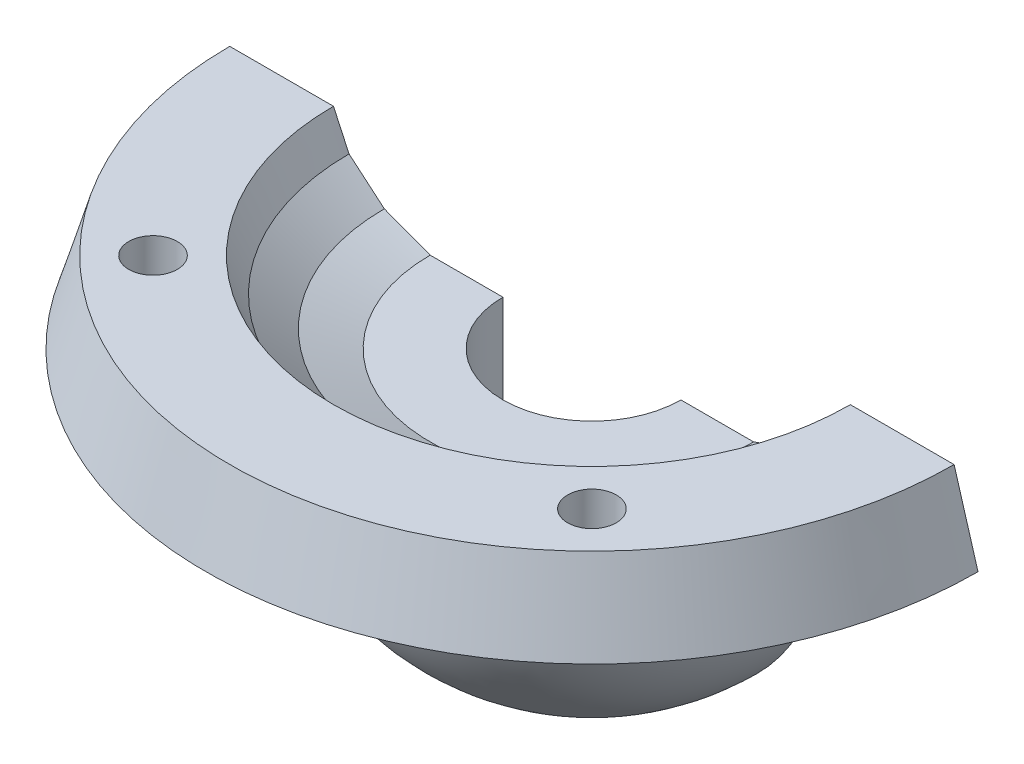
SolidWorks part; units mm, degrees
ref_plane "Front Plane" through (0, 0, 0) normal (0, 0, 1) x (1, 0, 0)
ref_plane "Top Plane" through (0, 0, 0) normal (0, 1, 0) x (1, 0, 0)
ref_plane "Right Plane" through (0, 0, 0) normal (1, 0, 0) x (0, 0, -1)
sketch "Sketch1" plane through (0, 0, 0) normal (0, 0, 1) x (1, 0, 0)
  line L0 (0, -14.5) -> (0, 2) construction
  line L1 (0, -55) -> (0, 55) construction
  line L2 (0, 2) -> (-14.3614, 2)
  line L3 (-5.5, 2) -> (-5.5, -3.5)
  line L4 (-5.5, -3.5) -> (-10, -3.5)
  line L5 (-10, -9.5) -> (0, -9.5)
  line L6 (0, -9.5) -> (0, 2)
  line L7 (-10, -9.5) -> (-10, -3.5)
  circle A0 centre (0, 0) radius 14.5
  dimension "D1" = 29
  dimension "D2" = 16.5
  dimension "D3" = 5.5
  dimension "D4" = 6
  dimension "D5" = 10
  dimension "D6" = 5.5
revolve "Revolve1" add sketch "Sketch1" angle 180 about L0
fillet "Fillet1" radius 2 1 edges at (0, -9.5, 10)
chamfer "Chamfer1" distance 4 angle 10 1 edges at (0, -3.5, 10)
sketch "Sketch2" plane through (0, 0, 0) normal (0, 0, 1) x (1, 0, 0)
  line L0 (-5.5, 2) -> (-10, 2)
  line L2 (-15.9743, 6.9835) -> (-15.0131, 4.9132)
  line L3 (-15.0131, 4.9132) -> (-12.8319, 3.0647)
  line L4 (-12.8319, 3.0647) -> (-10, 2)
  line L7 (0, -9.5) -> (0, 2) construction
  line L8 (-10, -9.5) -> (0, -9.5) construction
  line L10 (-5.5, -3.5) -> (-10, -3.5) construction
  line L11 (-5.5, 2) -> (-5.5, -3.5) construction
  line L13 (0, -9.5) -> (0, 2)
  line L14 (-5.9996, -9.5) -> (0, -9.5)
  line L15 (0, -9.5) -> (0, -14.5)
  line L16 (-5.5, -3.5) -> (-6.1423, -3.5)
  line L17 (-5.5, 2) -> (-5.5, -3.5)
  line L18 (-6.1423, -3.5) -> (-10, -4.2053)
  line L19 (-10, -4.2053) -> (-9.9996, -7.5)
  line L20 (-14.3637, 1.9835) -> (-23.8637, 1.9835)
  line L21 (-23.8637, 1.9835) -> (-22.3879, 6.9835)
  line L22 (-22.3879, 6.9835) -> (-19.3879, 6.9835)
  line L23 (-19.3879, 6.9835) -> (-15.9743, 6.9835)
  circle A1 centre (0, 0) radius 14.5
  arc A2 (-14.3637, 1.9835) -> (0, -14.5) centre (0, 0) ccw
  spline S0 degree 2 poles (728.886, 1849.3284) (76.6357, -22.5943) (-7.2006, -9.4078) (-7.8345, -9.308) (-8.3707, -9.1108) (-9.0147, -8.8739) (-9.4275, -8.5307) (-9.6843, -8.3173) (-9.8289, -8.0781) (-28.4244, 22.6912) (1978.088, 208.5551) knots -35.480489 -35.480489 -35.480489 0.25 0.25 0.5 0.5 0.75 0.75 0.875 0.875 14.48872 14.48872 14.48872 only from (-5.9996, -9.5) to (-9.9996, -7.5) construction
  spline S1 degree 2 poles (-5.9996, -9.5) (-6.614, -9.5) (-7.2006, -9.4078) (-7.8345, -9.308) (-8.3707, -9.1108) (-9.0147, -8.8739) (-9.4275, -8.5307) (-9.6843, -8.3173) (-9.8289, -8.0781) (-9.9996, -7.7956) (-9.9996, -7.5) knots 0 0 0 0.25 0.25 0.5 0.5 0.75 0.75 0.875 0.875 1 1 1
  dimension "D2" = 5
  dimension "D3" = 9.5
  dimension "D4" = 3
  dimension "D1" = 0
revolve "Revolve2" add sketch "Sketch2" angle 180 about L13
sketch "Sketch3" plane through (0, 6.9835, 0) normal (0, 1, 0) x (1, 0, 0)
  line L0 (0, 0) -> (15.8306, -15.8306) construction
  line L1 (-11.8159, 0) -> (11.8159, 0) construction
  arc A0 (-22.3879, 0) -> (22.3879, 0) centre (0, 0) ccw construction
  circle A1 centre (13.5647, -13.5647) radius 1.5
  dimension "D1" = 3
  dimension "D2" = 45
extrude "Cut-Extrude1" cut sketch "Sketch3" against normal blind 10
mirror "Mirror1" about plane through (0, 0, 0) normal (1, 0, 0) of "Cut-Extrude1"
delete or keep bodies "Body-Delete/Keep 1" type delete bodies bodies 101
